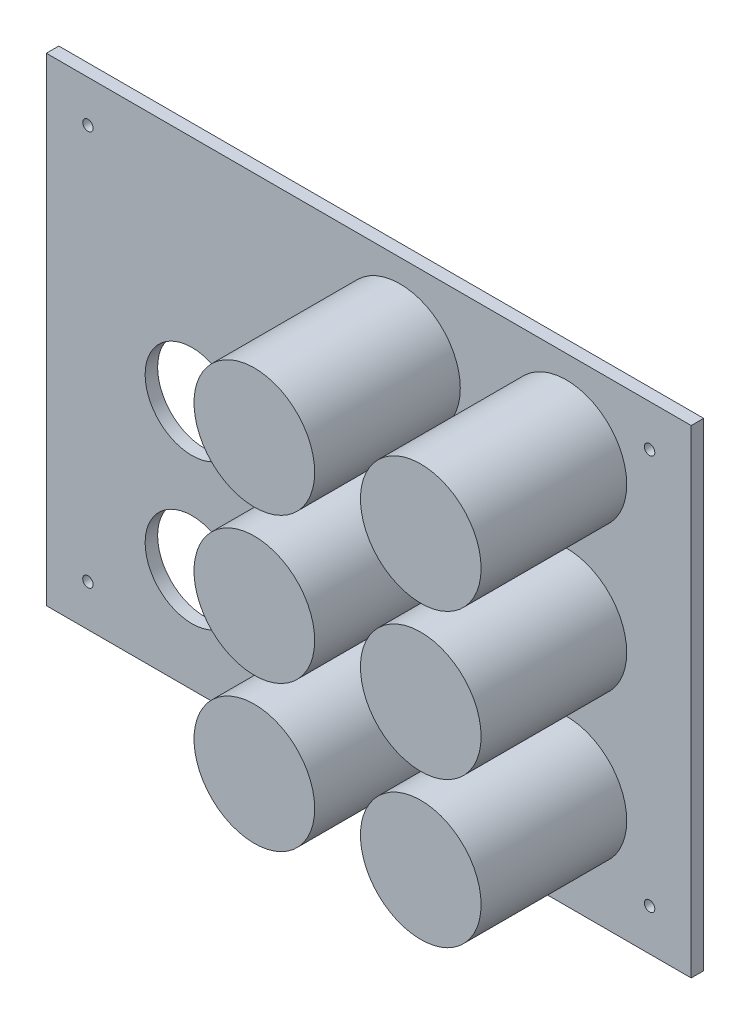
SolidWorks part; units mm, degrees
ref_plane "Plano frontal" through (0, 0, 0) normal (0, 0, 1) x (1, 0, 0)
ref_plane "Plano superior" through (0, 0, 0) normal (0, 1, 0) x (1, 0, 0)
ref_plane "Plano direito" through (0, 0, 0) normal (1, 0, 0) x (0, 0, -1)
sketch "Esboço1" plane through (0, 0, 0) normal (0, 0, 1) x (1, 0, 0)
  line L1 (-77.5, 57.5) -> (77.5, 57.5)
  line L2 (-77.5, 57.5) -> (-77.5, -57.5)
  line L3 (-77.5, -57.5) -> (77.5, -57.5)
  line L4 (77.5, 57.5) -> (77.5, -57.5)
  line L5 (-77.5, 57.5) -> (77.5, -57.5) construction
  line L6 (-77.5, -57.5) -> (77.5, 57.5) construction
  point P0 (0, 0)
  dimension "D1" = 115
  dimension "D2" = 155
extrude "Ressalto-extrusão1" add sketch "Esboço1" along normal blind 3
sketch "Esboço11" plane through (0, 0, 0) normal (0, 0, -1) x (-1, 0, 0)
  line L0 (-77.5, 57.5) -> (77.5, 57.5) construction
  line L2 (-77.5, -57.5) -> (-77.5, 57.5) construction
  circle A0 centre (-7.5, -32.5) radius 12.5
  circle A1 centre (-47.5, -32.5) radius 12.5
  circle A2 centre (-47.5, 2.5) radius 12.5
  circle A3 centre (-47.5, 37.5) radius 12.5
  circle A4 centre (-7.5, 37.5) radius 12.5
  circle A5 centre (-7.5, 2.5) radius 12.5
  dimension "D1" = 25
  dimension "D2" = 20
  dimension "D3" = 20
  dimension "D4" = 35
  dimension "D5" = 35
  dimension "D6" = 35
  dimension "D7" = 30
  dimension "D8" = 30
  dimension "D9" = 40
  dimension "D10" = 35
  dimension "D11" = 40
  dimension "D12" = 40
  dimension "D13" = 30
sketch "Esboço12" plane through (0, 0, 3) normal (0, 0, 1) x (1, 0, 0)
  circle A0 centre (7.5, 37.5) radius 14.5
  circle A1 centre (7.5, 37.5) radius 12.5 construction
  circle A2 centre (47.5, 37.5) radius 14.5
  circle A3 centre (7.5, 2.5) radius 14.5
  circle A4 centre (47.5, 2.5) radius 14.5
  circle A5 centre (47.5, -32.5) radius 14.5
  circle A6 centre (7.5, -32.5) radius 14.5
  dimension "D1" = 2
extrude "Ressalto-extrusão14" add sketch "Esboço12" along normal blind 35 separate body contours A3 | A4 | A0 | A2 | A5 | A6
extrude "Corte-extrusão8" cut sketch "Esboço11" against normal blind 35 contours A3
extrude "Corte-extrusão9" cut sketch "Esboço11<5>" against normal blind 35 contours A1 | A0 | A2 | A4 | A5
sketch "Esboço11<5>" plane through (0, 0, 0) normal (0, 0, -1) x (-1, 0, 0) same geometry as "Esboço11"
sketch "Esboço13" plane through (0, 0, 0) normal (0, 0, -1) x (-1, 0, 0)
  line L0 (77.5, 57.5) -> (77.5, -57.5) construction
  line L1 (77.5, -57.5) -> (-77.5, -57.5) construction
  circle A0 centre (42.5, -32.5) radius 11.25
  circle A1 centre (42.5, 2.5) radius 11.25
  dimension "D1" = 22.5
  dimension "D2" = 35
  dimension "D3" = 25
  dimension "D4" = 35
  dimension "D5" = 35
sketch "Esboço14" plane through (0, 0, 0) normal (0, 0, -1) x (-1, 0, 0)
  line L0 (77.5, -57.5) -> (-77.5, -57.5) construction
  line L1 (77.5, 57.5) -> (77.5, -57.5) construction
  line L2 (-77.5, 57.5) -> (77.5, 57.5) construction
  line L3 (-77.5, -57.5) -> (-77.5, 57.5) construction
  circle A0 centre (67.5, -47.5) radius 2.5
  circle A1 centre (67.5, 47.5) radius 2.5
  circle A2 centre (-67.5, 47.5) radius 2.5
  circle A3 centre (-67.5, -47.5) radius 2.5
  dimension "D1" = 5
  dimension "D2" = 10
  dimension "D3" = 10
  dimension "D4" = 10
  dimension "D5" = 10
  dimension "D6" = 10
  dimension "D7" = 10
  dimension "D8" = 10
  dimension "D9" = 10
hole_wizard "Rebaixo para parafuso de máquina com cabeça panela de #01" positions "3DSketch1" profile "Esboço15" counterbore size "#0" standard "Ansi Inch" end condition through all
sketch3d "3DSketch1"
  point P0 (-67.5, -47.5, 0)
  point P3 (-67.5, 47.5, 0)
  point P6 (67.5, 47.5, 0)
  point P9 (67.5, -47.5, 0)
sketch "Esboço15" plane through (-67.5, -47.5, 0) normal (1, 0, 0) x (0, 1, 0)
  line L0 (0, 0) -> (0, 38)
  line L1 (0, 38) -> (1.25, 38)
  line L3 (1.25, 38) -> (1.25, 1.1176)
  line L4 (1.7856, 1.1176) -> (1.25, 1.1176)
  line L5 (1.7856, 1.1176) -> (1.7856, 0.8218)
  line L6 (1.7856, 0.8218) -> (2.5, 0)
  line L7 (2.5, 0) -> (0, 0)
  line L8 (-1.7856, 0.8218) -> (-2.5, 0) construction
  line L11 (0, -6.35) -> (0, 107.95) construction
  dimension "Thru Hole Dia." = 2.5
  dimension "Thru Hole Depth" = 38
  dimension "C'Bore Dia." = 3.5712
  dimension "C'Bore Depth" = 1.1176
  dimension "Near C'Sink Dia." = 5
  dimension "Near C'Sink Angle" = 82
extrude "Botões" cut sketch "Esboço13" against normal up to next (3 mm away)
sketch "6" plane through (0, 0, 0) normal (0, 0, -1) x (-1, 0, 0)
  circle A0 centre (-27.5, 34.5) radius 1
  circle A1 centre (-27.5, 37.5) radius 1
  circle A2 centre (-27.5, 40.5) radius 1
  circle A3 centre (-24.5, 40.5) radius 1
  circle A4 centre (-33, 34.5) radius 1
  circle A5 centre (-30.5, 34.5) radius 1
  circle A6 centre (-47.5, 37.5) radius 12.5 construction
  circle A7 centre (-30.5, 37.5) radius 1
  dimension "D4" = 20
  dimension "D6" = 3
  dimension "D9" = 3
  dimension "D12" = 2
  dimension "D13" = 3
  dimension "D1" = 3
  dimension "D2" = 3
  dimension "D3" = 3
  dimension "D5" = 3
  dimension "D7" = 3
  dimension "D8" = 3
  dimension "D10" = 2.5
  dimension "D11" = 0
  dimension "D14" = 3
sketch "4" plane through (0, 0, 0) normal (0, 0, -1) x (-1, 0, 0)
  circle A0 centre (-27.5, -35.5) radius 1
  circle A1 centre (-27.5, -32.5) radius 1
  circle A2 centre (-27.5, -29.5) radius 1
  circle A3 centre (-24.5, -29.5) radius 1
  circle A4 centre (-33, -35.5) radius 1
  circle A5 centre (-30.5, -35.5) radius 1
  circle A6 centre (-47.5, -32.5) radius 12.5 construction
  circle A7 centre (-33, -32.5) radius 1
  dimension "D4" = 3
  dimension "D6" = 3
  dimension "D9" = 0
  dimension "D12" = 2
  dimension "D13" = 0
  dimension "D14" = 0
  dimension "D1" = 3
  dimension "D2" = 3
  dimension "D3" = 3
  dimension "D5" = 3
  dimension "D7" = 3
  dimension "D8" = 3
  dimension "D10" = 2.5
  dimension "D11" = 20
sketch "Esboço28" plane through (0, 0, 0) normal (0, 0, -1) x (-1, 0, 0)
  circle A0 centre (12.5, -0.5) radius 1
  circle A1 centre (12.5, 2.5) radius 1
  circle A2 centre (12.5, 5.5) radius 1
  circle A3 centre (15.5, 5.5) radius 1
  circle A4 centre (9.5, 2.5) radius 1
  circle A5 centre (9.5, -0.5) radius 1
  dimension "D4" = 20
  dimension "D6" = 3
  dimension "D9" = 3
  dimension "D12" = 2
  dimension "D1" = 3
  dimension "D2" = 3
  dimension "D3" = 3
  dimension "D5" = 3
  dimension "D7" = 3
  dimension "D8" = 3
  dimension "D10" = 3
  dimension "D11" = 0
sketch "Esboço29" plane through (0, 0, 0) normal (0, 0, -1) x (-1, 0, 0)
  circle A0 centre (12.5, -35.5) radius 1
  circle A1 centre (12.5, -32.5) radius 1
  circle A2 centre (12.5, -29.5) radius 1
  circle A3 centre (15.5, -29.5) radius 1
  circle A5 centre (9.5, -35.5) radius 1
  dimension "D4" = 20
  dimension "D6" = 3
  dimension "D9" = 3
  dimension "D12" = 2
  dimension "D1" = 3
  dimension "D2" = 3
  dimension "D3" = 3
  dimension "D5" = 3
  dimension "D8" = 3
  dimension "D11" = 0
extrude "Pino 1" add sketch "Esboço29" along normal blind 1.5
extrude "Pino 2" add sketch "Esboço28" along normal blind 1.5
sketch "3" plane through (0, 0, 0) normal (0, 0, -1) x (-1, 0, 0)
  circle A0 centre (12.5, 34.5) radius 1
  circle A1 centre (12.5, 37.5) radius 1
  circle A2 centre (12.5, 40.5) radius 1
  circle A3 centre (15.5, 40.5) radius 1
  circle A4 centre (7, 34.5) radius 1
  circle A5 centre (9.5, 34.5) radius 1
  circle A7 centre (-7.5, 37.5) radius 12.5 construction
  dimension "D4" = 20
  dimension "D6" = 3
  dimension "D9" = 3
  dimension "D12" = 2
  dimension "D1" = 3
  dimension "D2" = 3
  dimension "D3" = 3
  dimension "D5" = 3
  dimension "D7" = 3
  dimension "D8" = 3
  dimension "D10" = 2.5
  dimension "D11" = 0
extrude "Pino 3" add sketch "3" along normal blind 1.5
extrude "Pino 4" add sketch "4" along normal blind 1.5
sketch "5" plane through (0, 0, 0) normal (0, 0, -1) x (-1, 0, 0)
  circle A0 centre (-27.5, -0.5) radius 1
  circle A1 centre (-27.5, 2.5) radius 1
  circle A2 centre (-27.5, 5.5) radius 1
  circle A3 centre (-24.5, 5.5) radius 1
  circle A5 centre (-30.5, -0.5) radius 1
  circle A7 centre (-33, 2.5) radius 1
  dimension "D4" = 2.5
  dimension "D6" = 3
  dimension "D9" = 20
  dimension "D12" = 2
  dimension "D13" = 0
  dimension "D1" = 3
  dimension "D2" = 3
  dimension "D3" = 3
  dimension "D5" = 3
  dimension "D7" = 3
  dimension "D8" = 3
  dimension "D10" = 0
extrude "Pino 5" add sketch "5" along normal blind 1.5
extrude "Pino 6" add sketch "6" along normal blind 1.5
